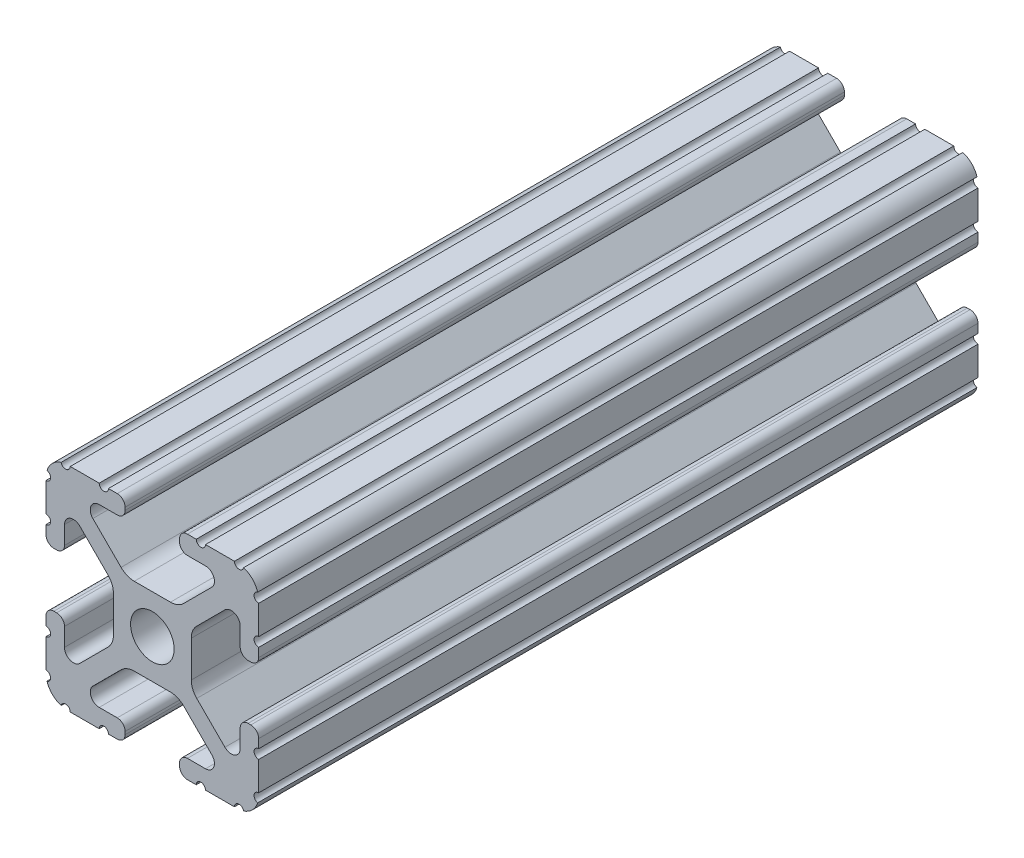
SolidWorks part; units mm, degrees
ref_plane "Front Plane" through (0, 0, 0) normal (0, 0, 1) x (1, 0, 0)
ref_plane "Top Plane" through (0, 0, 0) normal (0, 1, 0) x (1, 0, 0)
ref_plane "Right Plane" through (0, 0, 0) normal (1, 0, 0) x (0, 0, -1)
sketch "Sketch2" plane through (0, 0, 0) normal (0, 0, 1) x (1, 0, 0)
  line L0 (0, 12.7) -> (0, -12.7) construction
  line L1 (-12.7, 0) -> (12.7, 0) construction
  line L2 (3.2512, -12.7) -> (12.7, -12.7)
  line L3 (12.7, -12.7) -> (12.7, -3.2512)
  line L4 (3.2512, -12.7) -> (3.2512, -10.4902)
  line L5 (3.2512, -10.4902) -> (8.9276, -10.4902)
  line L6 (8.9276, -10.4902) -> (3.0856, -4.6482)
  line L7 (0, 0) -> (12.7, -12.7) construction
  line L8 (12.7, -3.2512) -> (10.4902, -3.2512)
  line L9 (10.4902, -3.2512) -> (10.4902, -8.9276)
  line L10 (10.4902, -8.9276) -> (4.6482, -3.0856)
  circle A0 centre (0, 0) radius 2.6035
  arc A1 (6.3485, -10.4902) -> (7.1039, -8.6665) centre (6.3485, -9.4219) ccw construction
  point P8 (0, -4.6482)
  dimension "Center Hole Diameter" = 5.207
  dimension "Rail Height" = 25.4
  dimension "Rail Width" = 25.4
  dimension "T-Slot Width" = 6.5024
  dimension "Slot Inner Width" = 14.8336
  dimension "Thickness" = 2.2098
  dimension "Slot Depth" = 5.842
  dimension "D1" = 2.2098
sketch "Sketch3" plane through (0, 0, 0) normal (1, 0, 0) x (0, 0, -1)
  line L0 (-76.2, -12.7) -> (76.2, -12.7) construction
  line L1 (-68.58, 0) -> (68.58, 0) construction
  dimension "Length" = 152.4
  dimension "D1" = 137.16
sketch "Sketch4" plane through (0, 0, 0) normal (0, 0, 1) x (1, 0, 0)
  line L0 (4.1904, -12.7) -> (10.1173, -12.7)
  line L1 (3.2512, -12.7) -> (12.7, -12.7) construction
  line L2 (3.2512, -12.7) -> (3.2512, -10.4902) construction
  line L3 (3.2512, -10.4902) -> (8.9276, -10.4902) construction
  line L4 (3.2512, -11.4294) -> (3.2512, -11.7608)
  line L5 (4.1904, -10.4902) -> (6.3485, -10.4902)
  line L6 (0, -4.6482) -> (2.164, -4.6482)
  line L7 (8.9276, -10.4902) -> (3.0856, -4.6482) construction
  line L8 (3.7373, -5.2999) -> (7.1039, -8.6665)
  line L9 (12.7, -12.7) -> (12.7, -3.2512) construction
  line L10 (10.4902, -8.9276) -> (4.6482, -3.0856) construction
  line L11 (10.4902, -3.2512) -> (10.4902, -8.9276) construction
  line L12 (10.4902, -6.3485) -> (10.4902, -4.1904)
  line L13 (12.7, -3.2512) -> (10.4902, -3.2512) construction
  line L14 (11.4294, -3.2512) -> (11.7608, -3.2512)
  line L15 (12.7, -4.1904) -> (12.7, -10.1173)
  line L16 (8.6665, -7.1039) -> (5.2999, -3.7373)
  line L17 (4.6482, 0) -> (4.6482, -2.164)
  line L18 (-12.7, 0) -> (12.7, 0) construction
  line L19 (0, -4.6482) -> (0, -2.6035)
  line L20 (0, 12.7) -> (0, -12.7) construction
  line L21 (4.6482, 0) -> (2.6035, 0)
  arc A0 (3.2512, -11.7608) -> (4.1904, -12.7) centre (4.1904, -11.7608) ccw
  arc A2 (3.2512, -11.4294) -> (4.1904, -10.4902) centre (4.1904, -11.4294) cw
  arc A3 (6.3485, -10.4902) -> (7.1039, -8.6665) centre (6.3485, -9.4219) ccw
  arc A4 (2.164, -4.6482) -> (3.7373, -5.2999) centre (2.164, -6.8732) cw
  arc A5 (10.1173, -12.7) -> (12.7, -10.1173) centre (10.1173, -10.1173) ccw
  arc A6 (8.6665, -7.1039) -> (10.4902, -6.3485) centre (9.4219, -6.3485) ccw
  arc A7 (10.4902, -4.1904) -> (11.4294, -3.2512) centre (11.4294, -4.1904) cw
  arc A8 (11.7608, -3.2512) -> (12.7, -4.1904) centre (11.7608, -4.1904) cw
  arc A9 (5.2999, -3.7373) -> (4.6482, -2.164) centre (6.8732, -2.164) cw
  circle A10 centre (0, 0) radius 2.6035 construction
  arc A11 (0, -2.6035) -> (2.6035, 0) centre (0, 0) ccw
  dimension "D1" = 2.5827
  dimension "D2" = 2.225
  dimension "D3" = 0.9392
extrude "Boss-Extrude1" add sketch "Sketch4" along normal mid plane 85.9
sketch "Sketch5" plane through (0, 0, 0) normal (0, 0, 1) x (1, 0, 0)
  line L0 (3.2512, -12.7) -> (12.7, -12.7) construction
  line L1 (4.1904, -10.4902) -> (6.3485, -10.4902) construction
  line L3 (0, 0) -> (12.7, -12.7) construction
  line L4 (6.3485, -10.4902) -> (6.3485, -12.7) construction
  line L5 (8.9276, -10.4902) -> (3.0856, -4.6482) construction
  circle A0 centre (10.3562, -12.7) radius 0.5524
  circle A1 centre (5.796, -12.7) radius 0.5524
  circle A2 centre (12.7, -10.3562) radius 0.5524
  circle A3 centre (12.7, -5.796) radius 0.5524
  point P10 (5.2694, -10.4902)
  point P12 (9.4219, -6.3485)
  dimension "D1" = 1.1049
extrude "Cut-Extrude1" cut sketch "Sketch5" against normal through all both and the other way through all
mirror "Mirror1" about plane through (0, 0, 0) normal (1, 0, 0) of bodies 137 134
mirror "Mirror2" about plane through (0, 0, 0) normal (0, 1, 0) of bodies 135
sketch "Sketch6" plane through (0, 0, 0) normal (0, 1, 0) x (1, 0, 0)
  line L0 (0, 42.95) -> (0, 30.25) construction
  line L1 (0, -42.95) -> (0, -30.25) construction
  line L4 (2.164, 42.95) -> (-2.164, 42.95)
  line L5 (-2.164, 42.95) -> (-2.164, -42.95)
  line L6 (-2.164, -42.95) -> (2.164, -42.95)
  line L7 (2.164, -42.95) -> (2.164, 42.95)
  line L8 (2.164, 42.95) -> (-2.164, 42.95) construction
  line L9 (-2.164, 42.95) -> (-2.164, -42.95) construction
  line L10 (-2.164, -42.95) -> (2.164, -42.95) construction
  line L11 (2.164, -42.95) -> (2.164, 42.95) construction
  circle A0 centre (0, -30.25) radius 2.555
  circle A1 centre (0, 30.25) radius 2.555
  dimension "D2" = 12.7
  dimension "D3" = 5.11
  dimension "D1" = 0
extrude "Cut-Extrude2" cut sketch "Sketch6" against normal through all both and the other way through all
sketch "Sketch7" plane through (0, 0, 0) normal (1, 0, 0) x (0, 0, -1)
  line L0 (-42.95, 0) -> (-17.55, 0) construction
  line L1 (-42.95, -2.164) -> (42.95, -2.164) construction
  line L6 (-42.95, -2.164) -> (-42.95, 2.164) construction
  line L7 (-42.95, 2.164) -> (42.95, 2.164) construction
  line L8 (42.95, -2.164) -> (42.95, 2.164) construction
  line L9 (-42.95, -2.164) -> (42.95, 2.164) construction
  line L10 (-42.95, 2.164) -> (42.95, -2.164) construction
  line L11 (42.95, 0) -> (17.55, 0) construction
  circle A2 centre (17.55, 0) radius 2.54
  circle A3 centre (-17.55, 0) radius 2.54
  point P0 (0, 0)
  dimension "D1" = 25.4
  dimension "D2" = 5.08
extrude "Cut-Extrude3" cut sketch "Sketch7" against normal through all both and the other way through all
equation "\"D1@Boss-Extrude1\"=8.59cm"
equation "\"D1@Sketch2\"=\"Thickness@Sketch2\""
equation "\"D2@Sketch4\"=\"Slot Inner Width@Sketch2\"*0.15"
equation "\"D1@Sketch4\"=\"D3@Sketch4\"*2.75"
equation "\"D3@Sketch4\"=\"Thickness@Sketch2\"*0.425"
equation "\"D1@Sketch5\"=\"Thickness@Sketch2\"*0.5"
equation "\"D1@Sketch3\"=\"Length@Sketch3\"*0.9"
